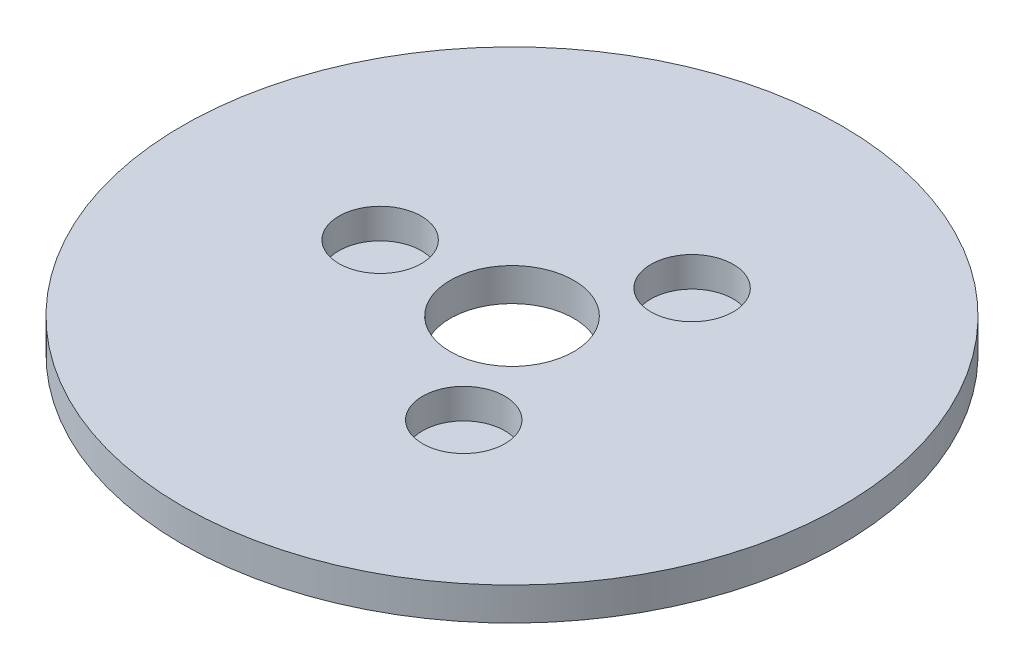
SolidWorks part; units mm, degrees
ref_plane "Front Plane" through (0, 0, 0) normal (0, 0, 1) x (1, 0, 0)
ref_plane "Top Plane" through (0, 0, 0) normal (0, 1, 0) x (1, 0, 0)
ref_plane "Right Plane" through (0, 0, 0) normal (1, 0, 0) x (0, 0, -1)
sketch "Sketch1" plane through (0, 0, 0) normal (0, 1, 0) x (1, 0, 0)
  circle A0 centre (0, 0) radius 80
  dimension "FLANGE_OD" = 160
extrude "Boss-Extrude1" add sketch "Sketch1" along normal blind 8
sketch "Sketch2" plane through (0, 0, 0) normal (0, 1, 0) x (1, 0, 0)
  circle A0 centre (0, 0) radius 15
  dimension "BORE_D" = 30
extrude "Cut-Extrude1" cut sketch "Sketch2" along normal through all
sketch "Sketch3" plane through (0, 8, 0) normal (0, 1, 0) x (1, 0, 0)
  circle A0 centre (0, 0) radius 32.0022 construction
  circle A1 centre (-32.0022, 0) radius 10
  dimension "BOLT_D" = 20
  dimension "BOLT_PCD" = 64.0044
extrude "Cut-Extrude2" cut sketch "Sketch3" against normal blind 7.2756
pattern_circular "CirPattern1" count 3 over 360 about axis through (0, 0, 0) along (0, 1, 0) of "Cut-Extrude2"
